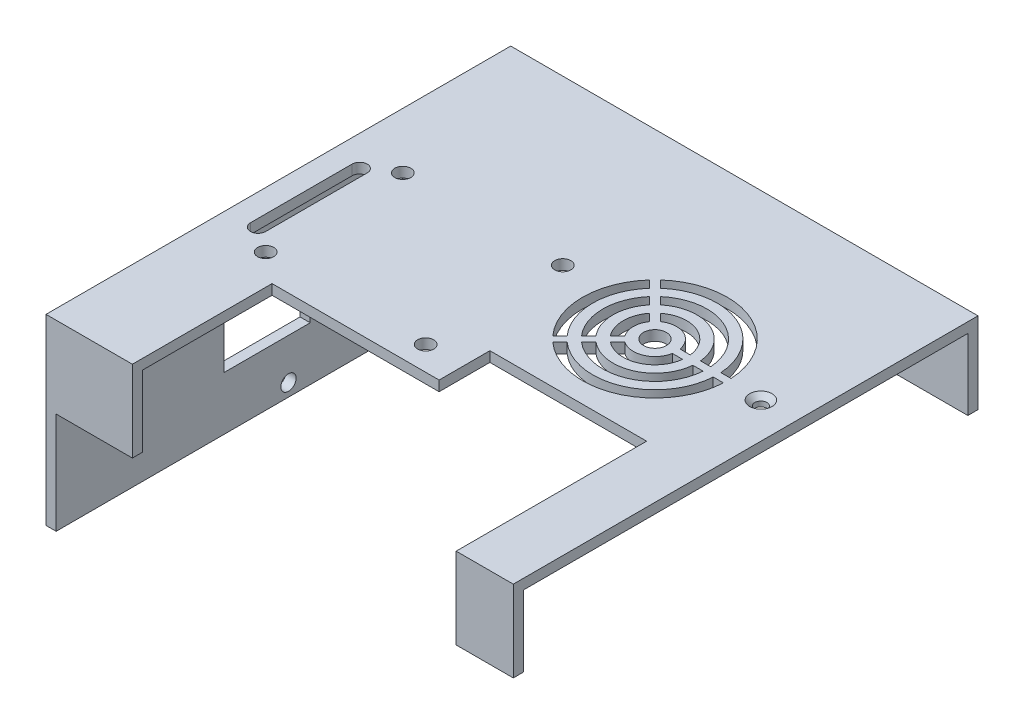
SolidWorks part; units mm, degrees
ref_plane "Front Plane" through (0, 0, 0) normal (0, 0, 1) x (1, 0, 0)
ref_plane "Top Plane" through (0, 0, 0) normal (0, 1, 0) x (1, 0, 0)
ref_plane "Right Plane" through (0, 0, 0) normal (1, 0, 0) x (0, 0, -1)
sketch "Sketch1" plane through (0, 0, 0) normal (0, 1, 0) x (1, 0, 0)
  line L1 (-45.5, -45.75) -> (45.5, -45.75)
  line L2 (-45.5, -45.75) -> (-45.5, 45.75)
  line L3 (-45.5, 45.75) -> (45.5, 45.75)
  line L4 (45.5, -45.75) -> (45.5, 45.75)
  line L5 (0, 45.75) -> (0, -45.75) construction
  line L6 (-45.5, 0) -> (45.5, 0) construction
  point P0 (0, 0)
  dimension "D1" = 91
  dimension "D2" = 91.5
extrude "Boss-Extrude1" add sketch "Sketch1" against normal blind 2
sketch "Sketch3" plane through (0, -2, 0) normal (0, -1, 0) x (1, 0, 0)
  line L0 (45.5, -45.75) -> (-45.5, -45.75) construction
  line L4 (-44.5082, 45.75) -> (-44.5082, -45.75)
  line L5 (-44.5082, 45.75) -> (-46.5082, 45.75)
  line L6 (-46.5082, 45.75) -> (-46.5082, -45.75)
  line L7 (-46.5082, -45.75) -> (-44.5082, -45.75)
  line L8 (-45.5, -45.75) -> (-45.5, 45.75) construction
  dimension "D1" = 2
extrude "Boss-Extrude3" add sketch "Sketch3" along normal blind 34
sketch "Sketch4" plane through (0, -2, 0) normal (0, -1, 0) x (-1, 0, 0)
  line L0 (44.5082, 45.75) -> (44.5082, -45.75) construction
  line L1 (-45.5, -45.75) -> (44.5082, -45.75)
  line L2 (-45.5, -45.75) -> (-45.5, -43.75)
  line L3 (-45.5, -43.75) -> (44.5082, -43.75)
  line L4 (44.5082, -45.75) -> (44.5082, -43.75)
  line L6 (-45.5, 45.75) -> (44.5082, 45.75)
  line L7 (-45.5, 45.75) -> (-45.5, 43.75)
  line L8 (-45.5, 43.75) -> (44.5082, 43.75)
  line L9 (44.5082, 45.75) -> (44.5082, 43.75)
  dimension "D1" = 2
  dimension "D2" = 2
extrude "Boss-Extrude4" add sketch "Sketch4" along normal blind 14
sketch "Sketch7" plane through (-45.5, 0, 0) normal (-1, 0, 0) x (0, 0, 1)
  line L0 (-40.75, -8.3824) -> (-24.75, -8.3824)
  line L1 (12.7279, -25.4485) -> (-4.2721, -25.4485)
  line L2 (12.7279, -25.4485) -> (12.7279, -10.8485)
  line L3 (12.7279, -10.8485) -> (-4.2721, -10.8485)
  line L4 (-4.2721, -25.4485) -> (-4.2721, -10.8485)
  line L5 (-22.45, -8.3824) -> (-6.45, -8.3824)
  line L6 (-22.45, -8.3824) -> (-22.45, -25.3824)
  line L7 (-22.45, -25.3824) -> (-6.45, -25.3824)
  line L8 (-6.45, -8.3824) -> (-6.45, -25.3824)
  line L9 (-24.75, -8.3824) -> (-24.75, -25.3824)
  line L10 (-40.75, -25.3824) -> (-24.75, -25.3824)
  line L11 (-40.75, -8.3824) -> (-40.75, -25.3824)
  line L12 (-45.75, -36) -> (-45.75, -2) construction
  dimension "D1" = 17
  dimension "D2" = 14.6
  dimension "D3" = 16
  dimension "D4" = 17
  dimension "D5" = 5
  dimension "D6" = 2.3
  dimension "D7" = 2.1779
extrude "Cut-Extrude3" cut sketch "Sketch7" against normal up to next and the other way up to next
sketch "Sketch15" plane through (0, 0, 0) normal (0, 1, 0) x (1, 0, 0)
  line L0 (17.9519, 10.7521) -> (31.8715, 10.7521)
  line L2 (3.3912, 26.2958) -> (31.8912, 26.2958) construction
  line L3 (3.3912, 26.2958) -> (3.3912, -6.2916) construction
  line L4 (3.3912, -6.2916) -> (31.8912, -6.2916) construction
  line L5 (31.8912, 26.2958) -> (31.8912, -6.2916) construction
  line L6 (17.6412, -6.2916) -> (17.6412, 26.2958) construction
  line L7 (3.3912, 10.0021) -> (31.8912, 10.0021) construction
  line L211 (17.9519, 9.2521) -> (31.8715, 9.2521)
  line L212 (17.6412, 10.0021) -> (7.5649, -0.0742) construction
  line L213 (17.6412, 10.0021) -> (7.5649, 20.0784) construction
  line L214 (7.0486, 19.5341) -> (16.5806, 10.0021)
  line L215 (8.1092, 20.5947) -> (17.9519, 10.7521)
  line L216 (16.5806, 10.0021) -> (7.0486, 0.4701)
  line L217 (17.9519, 9.2521) -> (8.1092, -0.5905)
  circle A0 centre (17.6412, 10.0021) radius 14.25
  circle A2 centre (17.6412, 10.0021) radius 12.25
  circle A10 centre (17.6412, 10.0021) radius 10.25
  circle A11 centre (17.6412, 10.0021) radius 8.25
  circle A12 centre (17.6412, 10.0021) radius 6.25
  circle A13 centre (17.6412, 10.0021) radius 4.25
  circle A14 centre (17.6412, 10.0021) radius 2.25
  dimension "D1" = 2
  dimension "D2" = 2
  dimension "D3" = 2
  dimension "D4" = 2
  dimension "D5" = 2
extrude "Cut-Extrude5" cut sketch "Sketch15" against normal up to next contours A2 L0 A0 L215 | A2 L217 A0 L211 | A2 L214 A0 L216 | A11 L214 A10 L216 | A13 L214 A12 L216 | L214 A14 L216 | A11 L0 A10 L215 | A13 L0 A12 L215 | L0 A14 L215 | L217 A14 L211 | A13 L217 A12 L211 | A11 L217 A10 L211 | L211 A14 L0 L215 L214 L216 L217
sketch "Sketch8" plane through (0, 0, 0) normal (0, 1, 0) x (1, 0, 0)
  circle A0 centre (38.5, 10.0021) radius 2
hole_wizard "CSK for M2 Flat Head Machine Screw1" positions "Sketch9" profile "Sketch11" countersink size "M2" standard "ANSI Metric" end condition up to next
sketch "Sketch9" plane through (0, 0, 0) normal (0, 1, 0) x (1, 0, 0)
  point P0 (38.5, 10.0021)
sketch "Sketch11" plane through (38.5, 0, -10.0021) normal (1, 0, 0) x (0, 0, 1)
  line L0 (0, 0) -> (0, 2)
  line L1 (0, 2) -> (1.2, 2)
  line L2 (1.2, 2) -> (1.2, 1)
  line L3 (1.2, 1) -> (2.2, 0)
  line L5 (2.2, 0) -> (0, 0)
  line L6 (-1.2, 1) -> (-2.2, 0) construction
  line L11 (0, -6.35) -> (0, 107.95) construction
  dimension "Thru Hole Dia." = 2.4
  dimension "Thru Hole Depth" = 2
  dimension "Near C'Sink Dia." = 4.4
  dimension "Near C'Sink Angle" = 90
sketch "Sketch12" plane through (0, 0, 0) normal (0, 1, 0) x (1, 0, 0)
  line L0 (-45.5, -45.75) -> (45.5, -45.75) construction
  line L5 (-29.5, -8.25) -> (34.25, -8.25) construction
  line L6 (-29.5, -45.75) -> (34.25, -45.75)
  line L7 (34.25, -45.75) -> (34.25, -8.25)
  line L9 (-29.5, -18.25) -> (-29.5, -45.75)
  line L10 (-29.5, -18.25) -> (3.3912, -18.25)
  line L11 (3.3912, -18.25) -> (3.3912, -8.25)
  line L12 (3.3912, -8.25) -> (34.25, -8.25)
  dimension "D2" = 63.75
  dimension "D3" = 37.5
  dimension "D4" = 10
extrude "Cut-Extrude4" cut sketch "Sketch12" against normal through all
sketch "Sketch17" plane through (45.5, 0, 0) normal (1, 0, 0) x (0, 0, -1)
  line L11 (-45.75, 0) -> (45.75, 0) construction
  line L12 (-17.5, -2) -> (17.5, -2)
  line L13 (-17.5, -2) -> (-17.5, 0)
  line L14 (-17.5, 0) -> (17.5, 0)
  line L15 (17.5, -2) -> (17.5, 0)
  line L16 (0, 0) -> (0, -2) construction
  line L17 (-17.5, -1) -> (17.5, -1) construction
  line L18 (-43.75, -2) -> (43.75, -2) construction
  line L19 (45.75, 0) -> (-45.75, 0) construction
  point P0 (0, -1)
  point P12 (0, 0)
  dimension "D1" = 35
sketch "Sketch18" plane through (0, 0, 0) normal (0, 1, 0) x (1, 0, 0)
  line L0 (-45.5, 45.75) -> (-45.5, -45.75) construction
  line L3 (-40.5, -10) -> (-40.5, 10) construction
  line L4 (-42, -10) -> (-42, 10)
  line L5 (-39, -10) -> (-39, 10)
  arc A0 (-42, -10) -> (-39, -10) centre (-40.5, -10) ccw
  arc A1 (-39, 10) -> (-42, 10) centre (-40.5, 10) ccw
  point P4 (0, 0)
  point P5 (-45.5, 0)
  point P9 (-40.5, 0)
  dimension "D1" = 20
  dimension "D2" = 5
  dimension "D4" = 3
extrude "Cut-Extrude6" cut sketch "Sketch18" against normal up to next
sketch "Sketch19" plane through (0, -2, 0) normal (0, 1, 0) x (1, 0, 0)
  line L0 (-45.5, 45.75) -> (-45.5, -45.75) construction
  line L1 (-4, -13.5) -> (-35.5, -13.5) construction
  line L2 (-4, -13.5) -> (-4, 13.5) construction
  line L3 (-4, 13.5) -> (-35.5, 13.5) construction
  line L4 (-35.5, -13.5) -> (-35.5, 13.5) construction
  line L5 (-19.75, 13.5) -> (-19.75, -13.5) construction
  line L6 (-4, 0) -> (-35.5, 0) construction
  line L9 (-32.3246, 13.5) -> (-33.9123, 16.25)
  line L10 (-33.9123, 16.25) -> (-37.0877, 16.25)
  line L11 (-37.0877, 16.25) -> (-38.6754, 13.5)
  line L12 (-38.6754, 13.5) -> (-37.0877, 10.75)
  line L13 (-37.0877, 10.75) -> (-33.9123, 10.75)
  line L14 (-33.9123, 10.75) -> (-32.3246, 13.5)
  line L21 (-7.1754, 13.5) -> (-5.5877, 10.75)
  line L22 (-5.5877, 10.75) -> (-2.4123, 10.75)
  line L23 (-2.4123, 10.75) -> (-0.8246, 13.5)
  line L24 (-0.8246, 13.5) -> (-2.4123, 16.25)
  line L25 (-2.4123, 16.25) -> (-5.5877, 16.25)
  line L26 (-5.5877, 16.25) -> (-7.1754, 13.5)
  line L27 (-0.8246, -13.5) -> (-2.4123, -10.75)
  line L28 (-2.4123, -10.75) -> (-5.5877, -10.75)
  line L29 (-5.5877, -10.75) -> (-7.1754, -13.5)
  line L30 (-7.1754, -13.5) -> (-5.5877, -16.25)
  line L31 (-5.5877, -16.25) -> (-2.4123, -16.25)
  line L32 (-2.4123, -16.25) -> (-0.8246, -13.5)
  line L33 (-32.3246, -13.5) -> (-33.9123, -10.75)
  line L34 (-33.9123, -10.75) -> (-37.0877, -10.75)
  line L35 (-37.0877, -10.75) -> (-38.6754, -13.5)
  line L36 (-38.6754, -13.5) -> (-37.0877, -16.25)
  line L37 (-37.0877, -16.25) -> (-33.9123, -16.25)
  line L38 (-33.9123, -16.25) -> (-32.3246, -13.5)
  circle A0 centre (-35.5, 13.5) radius 2.75 construction
  circle A1 centre (-4, 13.5) radius 2.75 construction
  circle A2 centre (-4, -13.5) radius 2.75 construction
  circle A3 centre (-35.5, -13.5) radius 2.75 construction
  circle A4 centre (-4, -13.5) radius 1.5877
  circle A5 centre (-4, 13.5) radius 1.5877
  circle A6 centre (-35.5, 13.5) radius 1.5877
  circle A7 centre (-35.5, -13.5) radius 1.5877
  point P0 (-19.75, 0)
  point P4 (0, 0)
  point P5 (-45.5, 0)
  dimension "D6" = 5.5
  dimension "D1" = 27
  dimension "D2" = 31.5
  dimension "D4" = 10
extrude "Cut-Extrude7" cut sketch "Sketch19" along normal up to next contours A4 | A5 | A6 | A7
sketch "Sketch22" plane through (0, -2, 0) normal (0, 1, 0) x (1, 0, 0)
  line L0 (-45.5, -45.75) -> (-46.5082, -45.75) construction
  line L1 (-45.5, 45.75) -> (-46.5082, 45.75)
  line L2 (-45.5, 45.75) -> (-45.5, -45.75)
  line L3 (-45.5, -45.75) -> (-46.5082, -45.75)
  line L4 (-46.5082, 45.75) -> (-46.5082, -45.75)
extrude "Boss-Extrude6" add sketch "Sketch22" along normal up to vertex (2 mm away) up to point (-45.5, 0, -45.75)
sketch "Sketch24" plane through (-46.5082, 0, 0) normal (-1, 0, 0) x (0, 0, 1)
  line L0 (-45.75, -36) -> (-45.75, -33.5) construction
  line L1 (-45.75, -36) -> (-45.75, 0) construction
  line L2 (0, -33.5) -> (-45.75, -33.5) construction
  circle A0 centre (0, -33.5) radius 1.5
extrude "Cut-Extrude8" cut sketch "Sketch24" against normal up to next
fillet "Fillet2" radius 1 8 edges at (-45.5082, -8.3824, -6.45) (-45.5082, -8.3824, -22.45) (-45.5082, -25.3824, -22.45) (-45.5082, -25.3824, -6.45) (-45.5082, -25.3824, -24.75) (-45.5082, -25.3824, -40.75) (-45.5082, -8.3824, -24.75) (-45.5082, -8.3824, -40.75) curvature continuous yes
